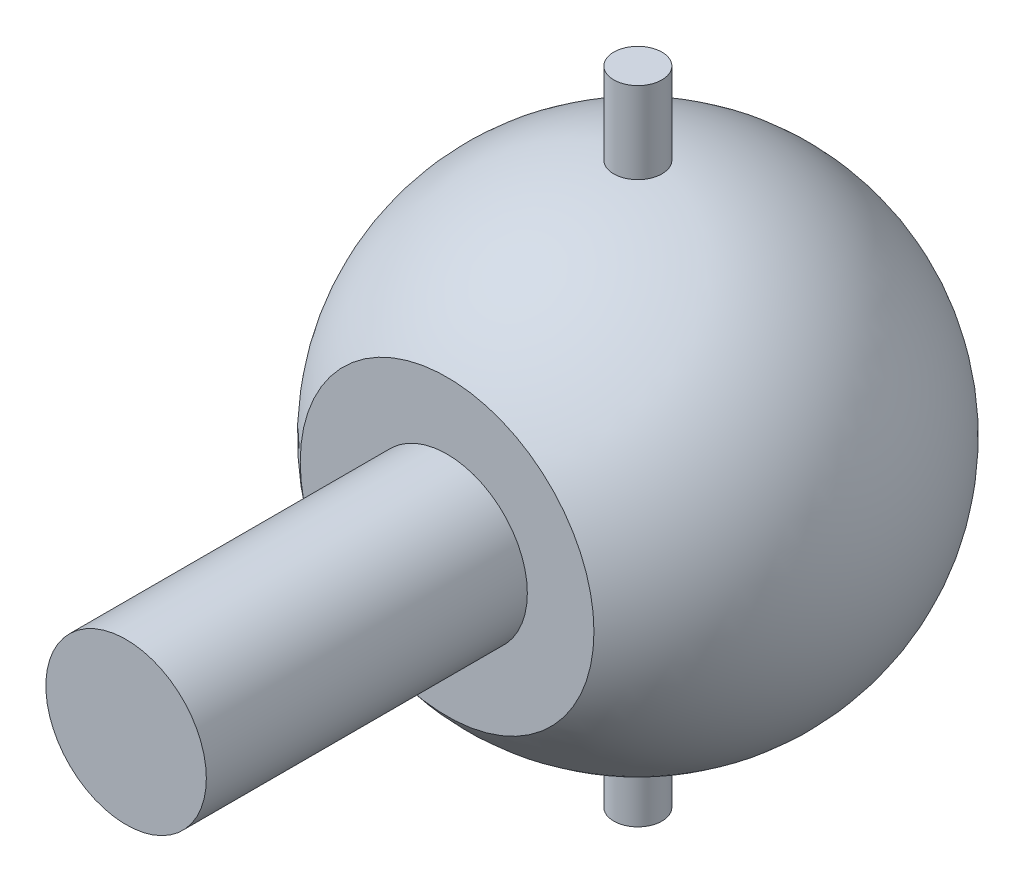
SolidWorks part; units mm, degrees
ref_plane "Alzado" through (0, 0, 0) normal (0, 0, 1) x (1, 0, 0)
ref_plane "Planta" through (0, 0, 0) normal (0, 1, 0) x (1, 0, 0)
ref_plane "Vista lateral" through (0, 0, 0) normal (1, 0, 0) x (0, 0, -1)
sketch "Croquis1" plane through (0, 0, 0) normal (0, 0, 1) x (1, 0, 0)
  line L1 (0, 15) -> (0, -15)
  circle A0 centre (0, 0) radius 25 construction
  circle A1 centre (0, 0) radius 20 construction
  arc A2 (0, -15) -> (0, 15) centre (0, 0) ccw
  dimension "D1" = 50
  dimension "D2" = 5
  dimension "D3" = 5
revolve "Revolución2" add sketch "Croquis1" angle 360 about L1
sketch "Croquis2" plane through (0, 0, 0) normal (1, 0, 0) x (0, 0, -1)
  line L0 (0, 0) -> (-15, 0) construction
  line L2 (-18.1146, -9.1508) -> (-11.8854, -9.1508)
  line L3 (-18.1146, -9.1508) -> (-18.1146, 9.1508)
  line L4 (-18.1146, 9.1508) -> (-11.8854, 9.1508)
  line L5 (-11.8854, -9.1508) -> (-11.8854, 9.1508)
  line L6 (-18.1146, -9.1508) -> (-11.8854, 9.1508) construction
  line L7 (-18.1146, 9.1508) -> (-11.8854, -9.1508) construction
  circle A0 centre (0, 0) radius 15 construction
  dimension "D1" = 15
extrude "Cortar-Extruir1" cut sketch "Croquis2" against normal blind 10 and the other way blind 15
sketch "Croquis3" plane through (0, 0, 0) normal (0, 1, 0) x (1, 0, 0)
  circle A0 centre (0, 0) radius 1.5
  dimension "D1" = 3
extrude "Saliente-Extruir1" add sketch "Croquis3" along normal blind 20 and the other way blind 20
sketch "Croquis4" plane through (0, 0, 11.8854) normal (0, 0, 1) x (1, 0, 0)
  circle A0 centre (0, 0) radius 5
  dimension "D1" = 10
extrude "Saliente-Extruir2" add sketch "Croquis4" along normal blind 20
sketch "Croquis5" plane through (0, 0, 0) normal (1, 0, 0) x (0, 0, -1)
  line L0 (0, 0) -> (-38.8591, 0)
